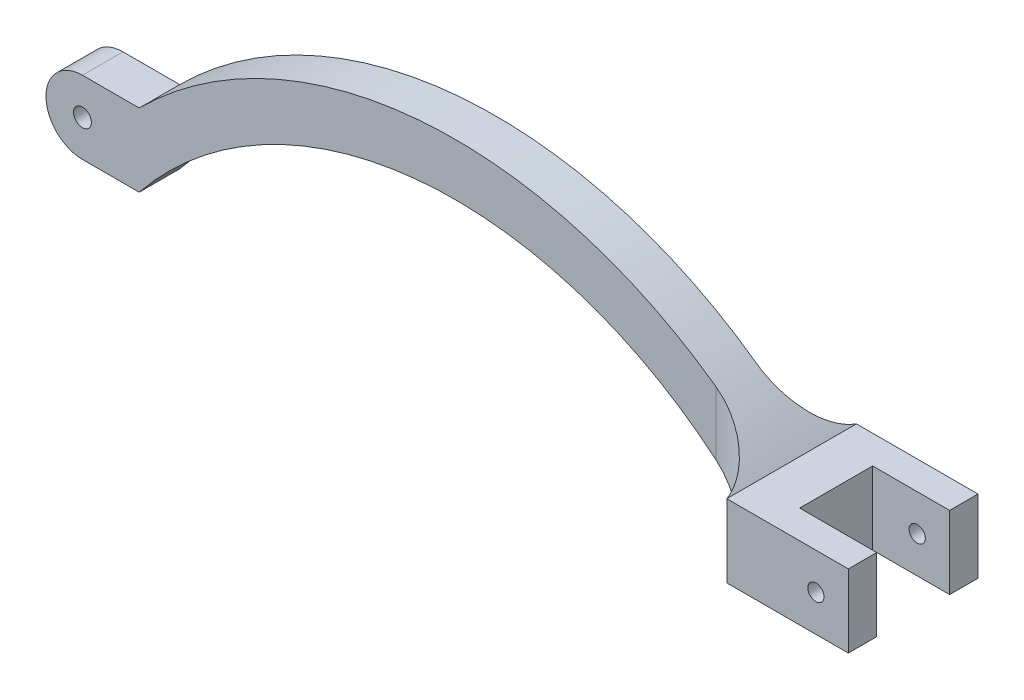
SolidWorks part; units mm, degrees
ref_plane "Front Plane" through (0, 0, 0) normal (0, 0, 1) x (1, 0, 0)
ref_plane "Top Plane" through (0, 0, 0) normal (0, 1, 0) x (1, 0, 0)
ref_plane "Right Plane" through (0, 0, 0) normal (1, 0, 0) x (0, 0, -1)
sketch "Sketch1" plane through (0, 0, 0) normal (0, 0, 1) x (1, 0, 0)
  line L0 (0, 0) -> (90, 0) construction
  line L1 (90, 4.5) -> (85, 4.5)
  line L3 (90, 4.5) -> (90, -4.5)
  line L4 (0, 4.5) -> (7, 4.5)
  line L5 (0, -4.5) -> (7, -4.5)
  circle A0 centre (0, 0) radius 1.1
  arc A1 (7, 4.5) -> (85, 4.5) centre (46, -34.5) cw
  circle A2 centre (0, 0) radius 4.5
  arc A3 (7, -4.5) -> (85, -4.5) centre (46, -35.789) cw
  dimension "D2" = 9
  dimension "D1" = 90
extrude "Boss-Extrude1" add sketch "Sketch1" along normal blind 5
sketch "Sketch3" plane through (0, 0, 5) normal (0, 0, 1) x (1, 0, 0)
  line L0 (90, 0) -> (90, -4.5)
  line L1 (90, -4.5) -> (85, -4.5)
  line L2 (85, -4.5) -> (80.9163, 0)
  line L3 (80.9163, 0) -> (90, 0)
extrude "Boss-Extrude2" add sketch "Sketch3" against normal blind 5
sketch "Sketch4" plane through (0, 4.5, 0) normal (0, 1, 0) x (1, 0, 0)
  line L0 (90, -5) -> (85, -5) construction
  line L2 (100, 2) -> (90.5, 2)
  line L3 (90, 5.5) -> (100, 5.5)
  line L4 (90, 5.5) -> (90, -10.5)
  line L5 (90, -10.5) -> (100, -10.5)
  line L6 (100, 5.5) -> (100, -10.5)
  line L7 (90, 5.5) -> (100, -10.5) construction
  line L8 (90, -10.5) -> (100, 5.5) construction
  line L9 (90.5, 2) -> (90.5, -7)
  line L10 (90.5, -7) -> (100, -7)
  point P4 (95, -2.5)
  line M11 (90, -5) -> (90, 0)
  dimension "D1" = 10
  dimension "D2" = 9.5
  dimension "D3" = 9
  dimension "D4" = 16
  dimension "D5" = 3.5
  dimension "D6" = 2.5
extrude "Boss-Extrude3" add sketch "Sketch4" against normal blind 9 contours L10 L9 L2 L6 L3 L4 L5 M11
sketch "Sketch5" plane through (0, 0, -5.5) normal (0, 0, -1) x (-1, 0, 0)
  line L0 (-100, -4.5) -> (-100, 4.5) construction
  line L1 (-90, 4.5) -> (-100, 4.5) construction
  circle A0 centre (-96, 0) radius 1
  dimension "D1" = 4
  dimension "D2" = 4.5
extrude "Cut-Extrude1" cut sketch "Sketch5" against normal blind 16
sketch "Sketch6" plane through (0, 0, -5.5) normal (0, 0, -1) x (-1, 0, 0)
  circle A0 centre (-96, 0) radius 1.9
extrude "Cut-Extrude2" cut sketch "Sketch6" against normal blind 1
fillet "Fillet1" radius 0.5 1 edges at (97, 0, 7)
sketch "Sketch7" plane through (0, -4.5, 0) normal (0, -1, 0) x (1, 0, 0)
  line L1 (90, 10.5) -> (85, 10.5)
  line L2 (90, 10.5) -> (90, -5.5)
  line L3 (90, -5.5) -> (85, -5.5)
  line L4 (85, 10.5) -> (85, -5.5)
extrude "Boss-Extrude4" add sketch "Sketch7" against normal blind 9
fillet "Fillet2" radius 7 2 edges at (85, 0, 0) (85, 0, 5)
